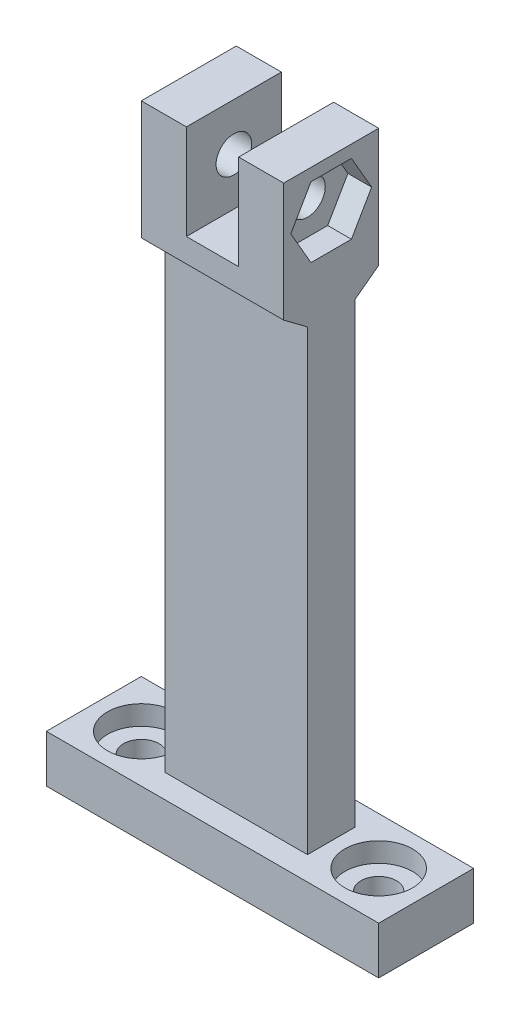
SolidWorks part; units mm, degrees
ref_plane "Alzado" through (0, 0, 0) normal (0, 0, 1) x (1, 0, 0)
ref_plane "Planta" through (0, 0, 0) normal (0, 1, 0) x (1, 0, 0)
ref_plane "Vista lateral" through (0, 0, 0) normal (1, 0, 0) x (0, 0, -1)
sketch "Croquis1" plane through (0, 0, 0) normal (0, 1, 0) x (1, 0, 0)
  line L0 (0, -10) -> (0, 10) construction
  line L1 (14, -4) -> (-14, -4)
  line L2 (14, -4) -> (14, 4)
  line L3 (14, 4) -> (-14, 4)
  line L4 (-14, -4) -> (-14, 4)
  line L5 (14, -4) -> (-14, 4) construction
  line L6 (14, 4) -> (-14, -4) construction
  line L7 (-6, -4) -> (-14, -4)
  line L8 (-6, -4) -> (-6, 4) construction
  line L9 (-6, 4) -> (-14, 4)
  line L10 (-14, -4) -> (-14, 4)
  line L11 (-6, -4) -> (-14, 4) construction
  line L12 (-6, 4) -> (-14, -4) construction
  line L13 (6, -4) -> (14, -4)
  line L14 (6, -4) -> (6, 4) construction
  line L15 (6, 4) -> (14, 4)
  line L16 (14, -4) -> (14, 4)
  line L17 (6, -4) -> (14, 4) construction
  line L18 (6, 4) -> (14, -4) construction
  circle A0 centre (-10, 0) radius 2.85
  circle A1 centre (-10, 0) radius 1.5
  circle A2 centre (10, 0) radius 1.5
  circle A3 centre (10, 0) radius 2.85
  point P0 (0, 0)
  point P5 (-10, 0)
  point P6 (10, 0)
  point P20 (0, 0)
  dimension "D5" = 5.7
  dimension "D6" = 3
  dimension "D1" = 28
  dimension "D2" = 8
  dimension "D3" = 8
  dimension "D4" = 8
  dimension "D7" = 4
extrude "Saliente-Extruir1" add sketch "Croquis1" along normal blind 4 contours L4 L1 L2 L3 A0 A3 | A0 A1 | A3 A2 region at (0, 0, 0) region at (-12.7694, 0, 0) region at (7.2306, 0, 0)
extrude "Cortar-Extruir1" cut sketch "Croquis1<3>" along normal through all from offset 2.35 contours A0 | A3
sketch "Croquis1<3>" plane through (0, 0, 0) normal (0, 1, 0) x (1, 0, 0) same geometry as "Croquis1"
sketch "Croquis2" plane through (0, 4, 0) normal (0, 1, 0) x (1, 0, 0)
  line L1 (6, -2) -> (-6, -2)
  line L2 (6, -2) -> (6, 2)
  line L3 (6, 2) -> (-6, 2)
  line L4 (-6, -2) -> (-6, 2)
  line L5 (6, -2) -> (-6, 2) construction
  line L6 (6, 2) -> (-6, -2) construction
  point P0 (0, 0)
  dimension "D1" = 12
  dimension "D2" = 4
extrude "Saliente-Extruir2" add sketch "Croquis2" along normal blind 40
sketch "Croquis3" plane through (0, 44, 0) normal (0, 1, 0) x (1, 0, 0)
  line L1 (6, -4) -> (-6, -4)
  line L2 (6, -4) -> (6, 4)
  line L3 (6, 4) -> (-6, 4)
  line L4 (-6, -4) -> (-6, 4)
  line L5 (6, -4) -> (-6, 4) construction
  line L6 (6, 4) -> (-6, -4) construction
  point P0 (0, 0)
  dimension "D1" = 12
  dimension "D2" = 8
extrude "Saliente-Extruir3" add sketch "Croquis3" along normal blind 10
sketch "Croquis4" plane through (0, 0, 4) normal (0, 0, 1) x (1, 0, 0)
  line L0 (-6, 54) -> (6, 54) construction
  line L1 (-2.2, 54) -> (2.2, 54)
  line L2 (-2.2, 54) -> (-2.2, 46)
  line L3 (-2.2, 46) -> (2.2, 46)
  line L4 (2.2, 54) -> (2.2, 46)
  line L5 (-2.2, 54) -> (2.2, 46) construction
  line L6 (-2.2, 46) -> (2.2, 54) construction
  line L7 (0, 54) -> (0, 44) construction
  line L8 (-6, 44) -> (6, 44) construction
  point P4 (0, 50)
  dimension "D1" = 8
  dimension "D2" = 4.4
extrude "Cortar-Extruir2" cut sketch "Croquis4" against normal through all
sketch "Croquis5" plane through (-6, 0, 0) normal (-1, 0, 0) x (0, 0, 1)
  line L0 (4, 54) -> (4, 44) construction
  line L1 (-4, 54) -> (4, 54) construction
  line L2 (-4, 54) -> (-4, 46) construction
  line L3 (-4, 46) -> (4, 46) construction
  line L4 (4, 54) -> (4, 46) construction
  line L5 (-4, 54) -> (4, 46) construction
  line L6 (-4, 46) -> (4, 54) construction
  circle A0 centre (0, 50) radius 2.85
  circle A1 centre (0, 50) radius 1.5
  point P4 (0, 50)
  dimension "D1" = 5.7
  dimension "D2" = 3
extrude "Cortar-Extruir7" cut sketch "Croquis5" along normal up to surface (-12 mm away) contours A1 region at (-6, 50, 0) up to face at (6, 36.5, 0)
extrude "Cortar-Extruir8" cut sketch "Croquis5<4>" against normal blind 1.54
sketch "Croquis5<4>" plane through (-6, 0, 0) normal (-1, 0, 0) x (0, 0, 1) same geometry as "Croquis5"
sketch "Croquis7" plane through (6, 0, 0) normal (1, 0, 0) x (0, 0, -1)
  line L0 (4, 54) -> (4, 44) construction
  line L1 (-4, 54) -> (4, 54) construction
  line L2 (-4, 54) -> (-4, 46) construction
  line L3 (-4, 46) -> (4, 46) construction
  line L4 (4, 54) -> (4, 46) construction
  line L5 (-4, 54) -> (4, 46) construction
  line L6 (-4, 46) -> (4, 54) construction
  line L8 (-3.4064, 50) -> (-1.7032, 47.05)
  line L9 (-1.7032, 47.05) -> (1.7032, 47.05)
  line L10 (1.7032, 47.05) -> (3.4064, 50)
  line L11 (3.4064, 50) -> (1.7032, 52.95)
  line L12 (1.7032, 52.95) -> (-1.7032, 52.95)
  line L13 (-1.7032, 52.95) -> (-3.4064, 50)
  circle A0 centre (0, 50) radius 2.95 construction
  point P4 (0, 50)
  dimension "D1" = 5.9
  dimension "D2" = 2.95
extrude "Cortar-Extruir9" cut sketch "Croquis7" against normal blind 2
sketch "Croquis8" plane through (6, 0, 0) normal (1, 0, 0) x (0, 0, -1)
  line L0 (-4, 44) -> (-2, 44)
  line L1 (-2, 44) -> (-2, 42.5)
  line L2 (-2, 44) -> (-2, 4) construction
  line L3 (-2, 42.5) -> (-4, 44)
  line L4 (0, 54) -> (0, 4) construction
  line L5 (-4, 54) -> (4, 54) construction
  line L6 (-2, 4) -> (2, 4) construction
  line L7 (2, 42.5) -> (4, 44)
  line L8 (2, 44) -> (2, 42.5)
  line L9 (4, 44) -> (2, 44)
  dimension "D1" = 1.5
extrude "Saliente-Extruir4" add sketch "Croquis8" against normal up to surface (12 mm away) up to face at (-6, 50, 2.85)
